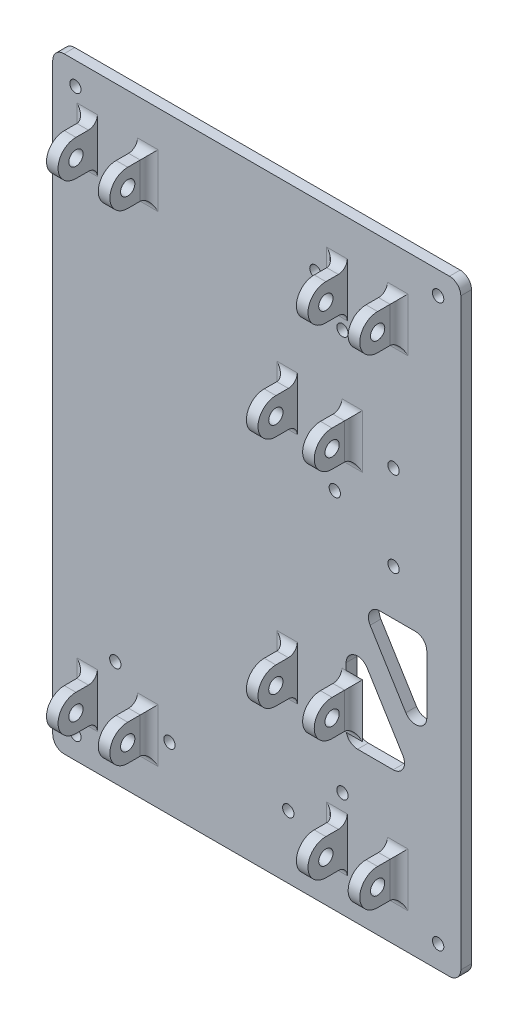
SolidWorks part; units mm, degrees
other "Markup3"
sketch "Sketch7" plane through (228.6, -342.9, 31.75) normal (0.076, -0.0024, 0.9971) x (0.9961, 0.0458, -0.0758)
other "Markup4"
sketch "Sketch8" plane through (228.6, -342.9, 31.75) normal (0.076, -0.0024, 0.9971) x (0.9961, 0.0458, -0.0758)
material "7075-T6 (SN)"
ref_plane "Front Plane" through (0, 0, 0) normal (0, 0, 1) x (1, 0, 0)
ref_plane "Top Plane" through (0, 0, 0) normal (0, 1, 0) x (1, 0, 0)
ref_plane "Right Plane" through (0, 0, 0) normal (1, 0, 0) x (0, 0, -1)
sketch "Sketch1" plane through (0, 0, 0) normal (0, 0, 1) x (1, 0, 0)
  line L1 (0, 0) -> (228.6, 0)
  line L2 (0, 0) -> (0, -339.725)
  line L3 (0, -339.725) -> (228.6, -339.725)
  line L4 (228.6, 0) -> (228.6, -339.725)
  dimension "D1" = 339.725
  dimension "D2" = 228.6
extrude "Boss-Extrude1" add sketch "Sketch1" along normal blind 6
sketch "Sketch2" plane through (0, 0, 6) normal (0, 0, 1) x (1, 0, 0)
  line L0 (0, 0) -> (0, -339.725) construction
  line L1 (25, -25.2425) -> (47.5, -25.2425) construction
  line L2 (25, -25.2425) -> (25, -45.2425)
  line L3 (25, -45.2425) -> (47.5, -45.2425) construction
  line L4 (47.5, -25.2425) -> (47.5, -45.2425)
  line L5 (165, -25.2425) -> (187.5, -25.2425) construction
  line L6 (165, -25.2425) -> (165, -45.2425)
  line L7 (165, -45.2425) -> (187.5, -45.2425) construction
  line L8 (187.5, -25.2425) -> (187.5, -45.2425)
  line L18 (137, -114.5325) -> (137, -225.1925) construction
  line L19 (0, -169.8625) -> (106.25, -169.8625) construction
  line L20 (54, -35.2425) -> (158.5, -35.2425) construction
  line L26 (165, -25.2425) -> (158.5, -25.2425)
  line L27 (165, -25.2425) -> (165, -45.2425)
  line L28 (165, -45.2425) -> (158.5, -45.2425)
  line L29 (158.5, -25.2425) -> (158.5, -45.2425)
  line L30 (187.5, -25.2425) -> (194, -25.2425)
  line L31 (187.5, -25.2425) -> (187.5, -45.2425)
  line L32 (187.5, -45.2425) -> (194, -45.2425)
  line L33 (194, -25.2425) -> (194, -45.2425)
  line L34 (47.5, -25.2425) -> (54, -25.2425)
  line L35 (47.5, -25.2425) -> (47.5, -45.2425)
  line L36 (47.5, -45.2425) -> (54, -45.2425)
  line L37 (54, -25.2425) -> (54, -45.2425)
  line L38 (25, -25.2425) -> (18.5, -25.2425)
  line L39 (25, -25.2425) -> (25, -45.2425)
  line L40 (25, -45.2425) -> (18.5, -45.2425)
  line L41 (18.5, -25.2425) -> (18.5, -45.2425)
  line L65 (228.6, -339.725) -> (228.6, 0) construction
  line L66 (137, -225.1925) -> (162, -225.1925) construction
  line L67 (158.5, -304.4825) -> (194, -304.4825) construction
  line L68 (149.5, -104.5325) -> (149.5, -235.1925) construction
  line L76 (18.5, -35.2425) -> (54, -35.2425) construction
  line L77 (18.5, -304.4825) -> (54, -304.4825) construction
  line L78 (36.25, -35.2425) -> (36.25, -304.4825) construction
  line L79 (137, -94.5325) -> (162, -94.5325) construction
  line L80 (54, -304.4825) -> (158.5, -304.4825) construction
  line L81 (106.25, -35.2425) -> (106.25, -304.4825) construction
  line L82 (106.25, -169.8625) -> (228.6, -169.8625) construction
  line L83 (130.5, -94.5325) -> (130.5, -114.5325)
  line L84 (137, -114.5325) -> (130.5, -114.5325)
  line L86 (137, -94.5325) -> (130.5, -94.5325)
  line L88 (137, -94.5325) -> (137, -114.5325)
  line L89 (162, -114.5325) -> (168.5, -114.5325)
  line L90 (162, -114.5325) -> (162, -94.5325)
  line L91 (168.5, -94.5325) -> (168.5, -114.5325)
  line L92 (162, -94.5325) -> (168.5, -94.5325)
  line L93 (130.5, -235.1925) -> (168.5, -235.1925) construction
  line L96 (137, -245.1925) -> (162, -245.1925) construction
  line L97 (162, -245.1925) -> (168.5, -245.1925)
  line L98 (168.5, -245.1925) -> (168.5, -225.1925)
  line L103 (130.5, -104.5325) -> (168.5, -104.5325) construction
  line L104 (137, -114.5325) -> (162, -114.5325) construction
  line L106 (158.5, -35.2425) -> (194, -35.2425) construction
  line L108 (176.25, -35.2425) -> (176.25, -304.4825) construction
  line L109 (165, -294.4825) -> (187.5, -294.4825) construction
  line L112 (165, -314.4825) -> (187.5, -314.4825) construction
  line L113 (25, -294.4825) -> (47.5, -294.4825) construction
  line L114 (25, -314.4825) -> (47.5, -314.4825) construction
  line L117 (162, -114.5325) -> (162, -225.1925) construction
  line L118 (18.5, -314.4825) -> (18.5, -294.4825)
  line L119 (25, -294.4825) -> (18.5, -294.4825)
  line L120 (25, -314.4825) -> (25, -294.4825)
  line L121 (25, -314.4825) -> (18.5, -314.4825)
  line L122 (54, -314.4825) -> (54, -294.4825)
  line L123 (47.5, -294.4825) -> (54, -294.4825)
  line L124 (47.5, -314.4825) -> (47.5, -294.4825)
  line L125 (47.5, -314.4825) -> (54, -314.4825)
  line L126 (194, -314.4825) -> (194, -294.4825)
  line L127 (187.5, -294.4825) -> (194, -294.4825)
  line L128 (187.5, -314.4825) -> (187.5, -294.4825)
  line L129 (187.5, -314.4825) -> (194, -314.4825)
  line L130 (158.5, -314.4825) -> (158.5, -294.4825)
  line L131 (165, -294.4825) -> (158.5, -294.4825)
  line L132 (165, -314.4825) -> (165, -294.4825)
  line L133 (165, -314.4825) -> (158.5, -314.4825)
  line L134 (187.5, -314.4825) -> (187.5, -294.4825)
  line L135 (165, -314.4825) -> (165, -294.4825)
  line L136 (47.5, -314.4825) -> (47.5, -294.4825)
  line L137 (25, -314.4825) -> (25, -294.4825)
  line L138 (162, -225.1925) -> (162, -245.1925)
  line L139 (162, -225.1925) -> (168.5, -225.1925)
  line L140 (137, -245.1925) -> (137, -225.1925)
  line L141 (137, -245.1925) -> (130.5, -245.1925)
  line L142 (137, -225.1925) -> (130.5, -225.1925)
  line L143 (130.5, -245.1925) -> (130.5, -225.1925)
  point P63 (194, -35.2425)
  point P101 (228.6, -169.8625)
  point P103 (158.5, -35.2425)
  dimension "D5" = 43.25
  dimension "D1" = 20
  dimension "D2" = 22.5
  dimension "D3" = 6.5
  dimension "D4" = 199.95
  dimension "D6" = 134.62
  dimension "D7" = 134.62
  dimension "D8" = 25
  dimension "D9" = 70
  dimension "D10" = 25
extrude "Boss-Extrude2" add sketch "Sketch2" along normal blind 24 contours L133 L132 L131 L130 | L128 L129 L126 L127 | L139 L138 L97 L98 | L143 L141 L140 L142 | L124 L125 L122 L123 | L121 L120 L119 L118 | L92 L90 L89 L91 | L88 L86 L83 L84 | L33 L30 L8 L32 | L37 L34 L4 L36 | L38 L41 L40 L2 | L26 L29 L28 L27 region at (21.75, -35.2425, 6) region at (50.75, -35.2425, 6) region at (190.75, -35.2425, 6) region at (133.75, -104.5325, 6) region at (165.25, -104.5325, 6) region at (165.25, -235.1925, 6) region at (21.75, -304.4825, 6) region at (50.75, -304.4825, 6) region at (190.75, -304.4825, 6) region at (161.75, -304.4825, 6) region at (133.75, -235.1925, 6)
sketch "Sketch3" plane through (18.5, 0, 0) normal (-1, 0, 0) x (0, 0, 1)
  line L0 (18, -104.5325) -> (6, -104.5325) construction
  line L1 (18, -304.4825) -> (6, -304.4825) construction
  line L2 (22, -235.1925) -> (37.7332, -235.1925) construction
  line L3 (22, -235.1925) -> (6, -235.1925) construction
  line L4 (18, -35.2425) -> (6, -35.2425) construction
  line L5 (6, -25.2425) -> (6, -45.2425) construction
  line L6 (6, -245.1925) -> (6, -225.1925) construction
  line L7 (6, 0) -> (6, -339.725) construction
  line L9 (18, -25.2425) -> (18, -12.9829)
  line L10 (18, -12.9829) -> (51.9495, -12.9829)
  line L11 (6, -245.1925) -> (6, -225.1925) construction
  line L12 (51.9495, -12.9829) -> (51.9495, -57.481)
  line L13 (51.9495, -57.481) -> (18, -57.481)
  line L14 (18, -57.481) -> (18, -45.2425)
  line L15 (52.4423, -132.3991) -> (18, -132.3991)
  line L16 (18, -94.5325) -> (18, -71.5915)
  line L17 (18, -71.5915) -> (52.4423, -71.5915)
  line L18 (18, -132.3991) -> (18, -114.5325)
  line L19 (52.4423, -71.5915) -> (52.4423, -132.3991)
  line L20 (52.5995, -270.3754) -> (18, -270.3754)
  line L21 (18, -225.1925) -> (18, -207.3064)
  line L22 (18, -207.3064) -> (52.5995, -207.3064)
  line L23 (18, -270.3754) -> (18, -245.1925)
  line L24 (52.5995, -207.3064) -> (52.5995, -270.3754)
  line L25 (52.621, -326.7211) -> (18, -326.7211)
  line L26 (18, -294.4825) -> (18, -282.2228)
  line L27 (18, -282.2228) -> (52.621, -282.2228)
  line L28 (18, -326.7211) -> (18, -314.4825)
  line L29 (52.621, -282.2228) -> (52.621, -326.7211)
  line L30 (6, -94.5325) -> (6, -114.5325) construction
  line L31 (30, -25.2425) -> (6, -25.2425) construction
  line L32 (30, -94.5325) -> (6, -94.5325) construction
  line L35 (6, -314.4825) -> (6, -294.4825) construction
  line L36 (6, -314.4825) -> (6, -294.4825) construction
  line L37 (18, -35.2425) -> (18, -104.5325) construction
  line L38 (18, -104.5325) -> (18, -235.1925) construction
  line L39 (18, -235.1925) -> (18, -304.4825) construction
  line L41 (30, -225.1925) -> (6, -225.1925) construction
  circle A0 centre (18, -35.2425) radius 4
  circle A1 centre (18, -235.1925) radius 4
  circle A2 centre (18, -35.2425) radius 5.5 construction
  circle A3 centre (18, -304.4825) radius 4
  circle A4 centre (18, -104.5325) radius 4
  arc A5 (18, -45.2425) -> (18, -25.2425) centre (18, -35.2425) ccw
  arc A6 (18, -114.5325) -> (18, -94.5325) centre (18, -104.5325) ccw
  arc A7 (18, -245.1925) -> (18, -225.1925) centre (18, -235.1925) ccw
  arc A8 (18, -314.4825) -> (18, -294.4825) centre (18, -304.4825) ccw
  point P62 (6, -304.4825)
  point P67 (6, -235.1925)
  dimension "D1" = 8
  dimension "D2" = 8
  dimension "D4" = 11
  dimension "D3" = 12
extrude "Cut-Extrude1" cut sketch "Sketch3" against normal through all both and the other way through all
fillet "Fillet2" radius 5 36 edges at (158.5, -304.4825, 6) (18.5, -304.4825, 6) (21.75, -45.2425, 6) (18.5, -35.2425, 6) (21.75, -25.2425, 6) (50.75, -25.2425, 6) (50.75, -45.2425, 6) (54, -35.2425, 6) (161.75, -25.2425, 6) (190.75, -25.2425, 6) (194, -35.2425, 6) (190.75, -45.2425, 6) (161.75, -45.2425, 6) (158.5, -35.2425, 6) (168.5, -104.5325, 6) (165.25, -114.5325, 6) (133.75, -114.5325, 6) (130.5, -104.5325, 6) (165.25, -94.5325, 6) (133.75, -94.5325, 6) (21.75, -294.4825, 6) (50.75, -294.4825, 6) (54, -304.4825, 6) (194, -304.4825, 6) (161.75, -294.4825, 6) (190.75, -294.4825, 6) (190.75, -314.4825, 6) (161.75, -314.4825, 6) (50.75, -314.4825, 6) (21.75, -314.4825, 6) (165.25, -225.1925, 6) (133.75, -225.1925, 6) (130.5, -235.1925, 6) (133.75, -245.1925, 6) (165.25, -245.1925, 6) (168.5, -235.1925, 6)
sketch "Sketch5" plane through (0, 0, 6) normal (0, 0, 1) x (1, 0, 0)
  line L0 (228.6, 0) -> (0, 0) construction
  line L1 (0, 0) -> (0, -339.725) construction
  line L2 (228.6, -339.725) -> (228.6, 0) construction
  line L3 (153.5, -50.2425) -> (153.5, -20.2425) construction
  line L4 (153.5, -50.2425) -> (153.5, -20.2425)
  line L6 (153.5, -35.2425) -> (59, -35.2425) construction
  line L7 (59, -20.2425) -> (59, -50.2425) construction
  line L8 (162.306, -49.7675) -> (162.306, -77.4398) construction
  line L9 (10.85, -50.2425) -> (59, -50.2425) construction
  line L10 (25, -50.2425) -> (13.5, -50.2425) construction
  line L11 (34.925, -50.2425) -> (34.925, -74.5657) construction
  line L12 (186.728, -115.063) -> (195.112, -115.063) construction
  line L13 (195.112, -115.063) -> (190.92, -115.063) construction
  line L14 (190.92, -115.063) -> (190.92, -77.4398) construction
  line L15 (190.92, -77.4398) -> (190.92, -189.3922) construction
  line L18 (160.654, -286.9575) -> (163.958, -286.9575) construction
  line L19 (33.4, -286.9575) -> (36.704, -286.9575) construction
  line L20 (36.704, -286.9575) -> (35.052, -286.9575) construction
  line L21 (35.052, -286.9575) -> (35.052, -271.8353) construction
  line L22 (162.306, -286.9575) -> (162.306, -271.8353) construction
  line L23 (59.054, -304.4825) -> (138.304, -304.4825) construction
  line L26 (0, -339.725) -> (228.6, -339.725) construction
  circle A0 centre (12.7, -12.7) radius 3.175
  circle A1 centre (215.9, -12.7) radius 3.175
  circle A2 centre (65.35, -35.2425) radius 3.175
  circle A3 centre (147.15, -35.2425) radius 3.175
  circle A4 centre (162.306, -56.1175) radius 3.175
  circle A5 centre (34.925, -56.5925) radius 3.175
  circle A6 centre (190.92, -108.713) radius 3.175
  circle A7 centre (158.028, -136.1329) radius 3.175
  circle A8 centre (190.92, -156.463) radius 3.175
  circle A9 centre (35.052, -280.6075) radius 3.175
  circle A10 centre (65.404, -304.4825) radius 3.175
  circle A11 centre (12.7, -327.025) radius 3.175
  circle A12 centre (215.9, -327.025) radius 3.175
  circle A13 centre (131.954, -304.4825) radius 3.175
  circle A14 centre (162.306, -280.6075) radius 3.175
  dimension "D1" = 12.7
  dimension "D3" = 12.7
  dimension "D5" = 6.35
  dimension "D6" = 6.35
  dimension "D7" = 6.35
  dimension "D9" = 6.35
  dimension "D14" = 6.35
  dimension "D15" = 6.35
  dimension "D17" = 12.7
  dimension "D18" = 12.7
  dimension "D19" = 12.7
  dimension "D2" = 12.7
  dimension "D4" = 12.7
  dimension "D16" = 12.7
extrude "Cut-Extrude2" cut sketch "Sketch5" against normal through all contours A0 | A5 | A3 | A1 | A4 | A6 | A7 | A8 | A12 | A14 | A13 | A10 | A9 | A11 region at (12.7, -12.7, 6) region at (215.9, -12.7, 6) region at (147.15, -35.2425, 6) region at (162.306, -56.1175, 6) region at (34.925, -56.5925, 6) region at (190.92, -108.713, 6) region at (158.028, -136.1329, 6) region at (190.92, -156.463, 6) region at (35.052, -280.6075, 6) region at (65.404, -304.4825, 6) region at (12.7, -327.025, 6) region at (215.9, -327.025, 6) region at (131.954, -304.4825, 6) region at (162.306, -280.6075, 6)
sketch "Sketch9" plane through (0, 0, 6) normal (0, 0, 1) x (1, 0, 0)
  line L5 (228.6, -339.725) -> (228.6, 0) construction
  line L6 (164.378, -181.863) -> (209.55, -181.863)
  line L7 (164.378, -181.863) -> (164.378, -255.2075)
  line L8 (164.378, -255.2075) -> (209.55, -255.2075)
  line L9 (209.55, -181.863) -> (209.55, -255.2075)
  line L10 (164.378, -181.863) -> (209.55, -255.2075)
  line L11 (171.8357, -181.863) -> (209.55, -243.0986)
  line L12 (164.378, -193.9719) -> (202.0923, -255.2075)
  line L14 (158.9712, -185.193) -> (204.1432, -258.5375) construction
  line L15 (169.7848, -178.533) -> (214.9568, -251.8775) construction
  circle A3 centre (162.306, -280.6075) radius 3.175 construction
  circle A4 centre (190.92, -156.463) radius 3.175 construction
  dimension "D4" = 25.4
  dimension "D7" = 25.4
  dimension "D6" = 19.05
  dimension "D8" = 6.35
  dimension "D9" = 6.35
extrude "Cut-Extrude3" cut sketch "Sketch9" against normal through all contours L12 L7 L8 | L6 L11 L9 region at (196.9786, -202.2749, 6) region at (176.9494, -234.7956, 6)
fillet "Fillet4" radius 6.35 10 edges at (228.6, -339.725, 3) (0, -339.725, 3) (0, 0, 3) (228.6, 0, 3) (171.8357, -181.863, 3) (209.55, -181.863, 3) (209.55, -243.0986, 3) (164.378, -193.9719, 3) (202.0923, -255.2075, 3) (164.378, -255.2075, 3)
move or copy body "Body-Move/Copy2" [suppressed] bodies to move or copy 105
move or copy body "Body-Move/Copy1" [suppressed] bodies to move or copy 105
